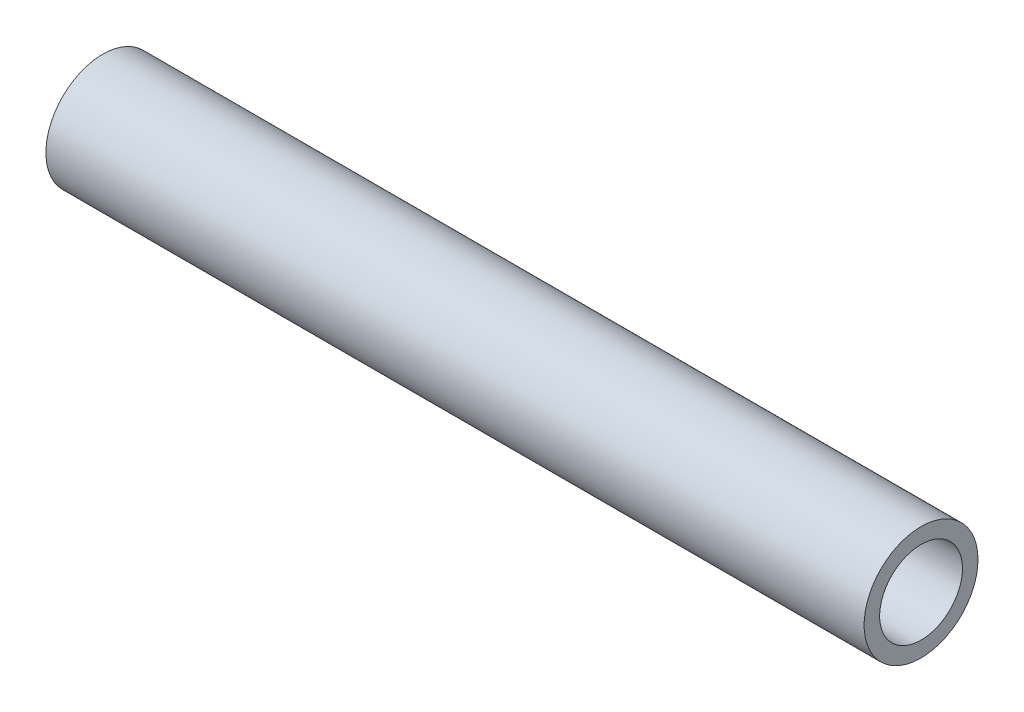
SolidWorks part; units mm, degrees
material "PVC Rígido"
ref_plane "Alzado" through (0, 0, 0) normal (0, 0, 1) x (1, 0, 0)
ref_plane "Planta" through (0, 0, 0) normal (0, 1, 0) x (1, 0, 0)
ref_plane "Vista lateral" through (0, 0, 0) normal (1, 0, 0) x (0, 0, -1)
sketch "Croquis1" plane through (0, 0, 0) normal (1, 0, 0) x (0, 0, -1)
  circle A0 centre (0, 0) radius 16.7
  circle A1 centre (0, 0) radius 12.15
  dimension "D1" = 33.4
  dimension "D2" = 24.3
extrude "Saliente-Extruir1" add sketch "Croquis1" along normal blind 240
